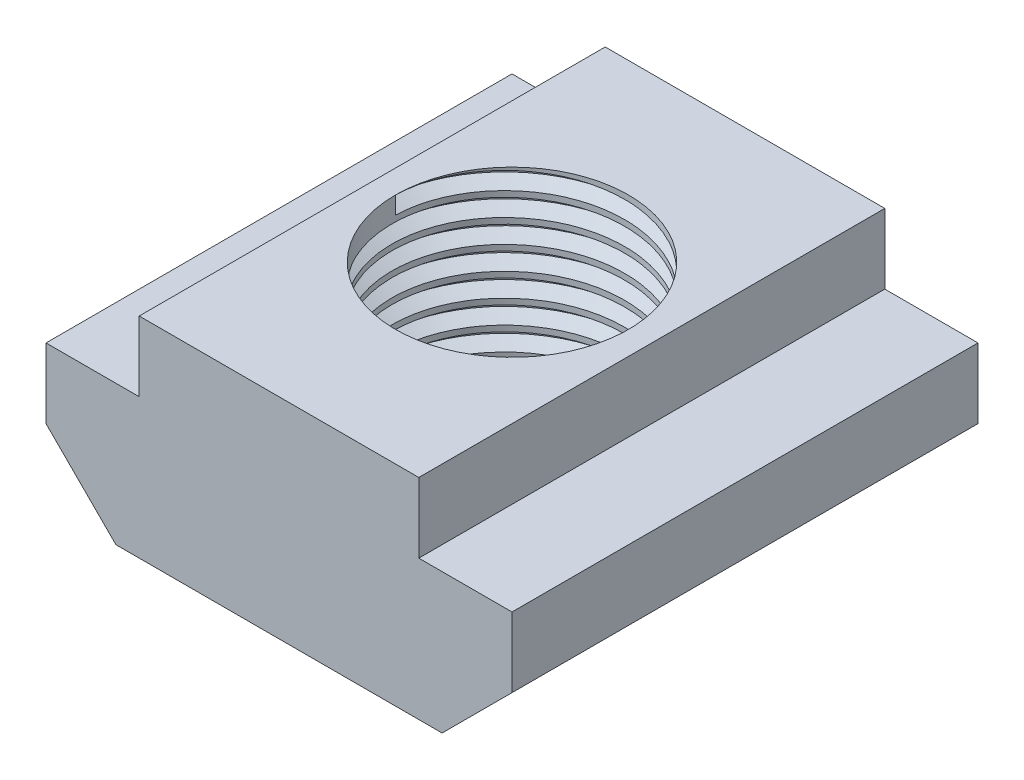
SolidWorks part; units mm, degrees
ref_plane "Front Plane" through (0, 0, 0) normal (0, 0, 1) x (1, 0, 0)
ref_plane "Top Plane" through (0, 0, 0) normal (0, 1, 0) x (1, 0, 0)
ref_plane "Right Plane" through (0, 0, 0) normal (1, 0, 0) x (0, 0, -1)
sketch "Sketch1" plane through (0, 0, 0) normal (0, 0, 1) x (1, 0, 0)
  line L8 (0, 0) -> (7, 0)
  line L9 (7, 0) -> (8.5, 1.5)
  line L10 (8.5, 1.5) -> (8.5, 3)
  line L11 (8.5, 3) -> (6.5, 3)
  line L12 (6.5, 3) -> (6.5, 4.5)
  line L13 (6.5, 4.5) -> (0.5, 4.5)
  line L14 (0.5, 4.5) -> (0.5, 3)
  line L15 (0.5, 3) -> (-1.5, 3)
  line L16 (-1.5, 3) -> (-1.5, 1.5)
  line L17 (-1.5, 1.5) -> (0, 0)
  dimension "D1" = 4.5
  dimension "D2" = 10
  dimension "D3" = 6
  dimension "D4" = 3
  dimension "D5" = 135
  dimension "D6" = 135
  dimension "D7" = 1.5
extrude "Boss-Extrude1" add sketch "Sketch1" along normal blind 10
sketch "Sketch2" plane through (0, 4.5, 0) normal (0, 1, 0) x (1, 0, 0)
  line L0 (0.5, 0) -> (6.5, -10) construction
  circle A0 centre (3.5, -5) radius 2.5
  dimension "D1" = 5
extrude "Cut-Extrude1" cut sketch "Sketch2" against normal through all
thread "Thread1" pitch 0.5 method cut profile "Thread Profile2" start angle 0, offset 0, length 0, pitch 0.5, diameter 5
ref_plane "Plane2" through (1, 4.5, 5) normal (0, 0, 1) x (-1, 0, 0)
sketch "Thread Profile2" plane through (1, 4.5, 5) normal (0, 0, 1) x (-1, 0, 0)
  line L0 (0, 0) -> (0, 0.5) construction
  line L1 (0, 0) -> (0.2706, 0.1562)
  line L2 (0.2706, 0.1562) -> (0.2706, 0.2187)
  line L3 (0.2706, 0.2187) -> (0, 0.375)
  line L4 (0.2706, 0.1875) -> (0, 0.1875) construction
  line L11 (0, 0) -> (0, 0.375)
  point P2 (0, 0)
  dimension "Pitch" = 0.5
  dimension "Profile_Angle" = 60
  dimension "Profile_Land" = 0.0625
  dimension "Profile_Height" = 0.2706
